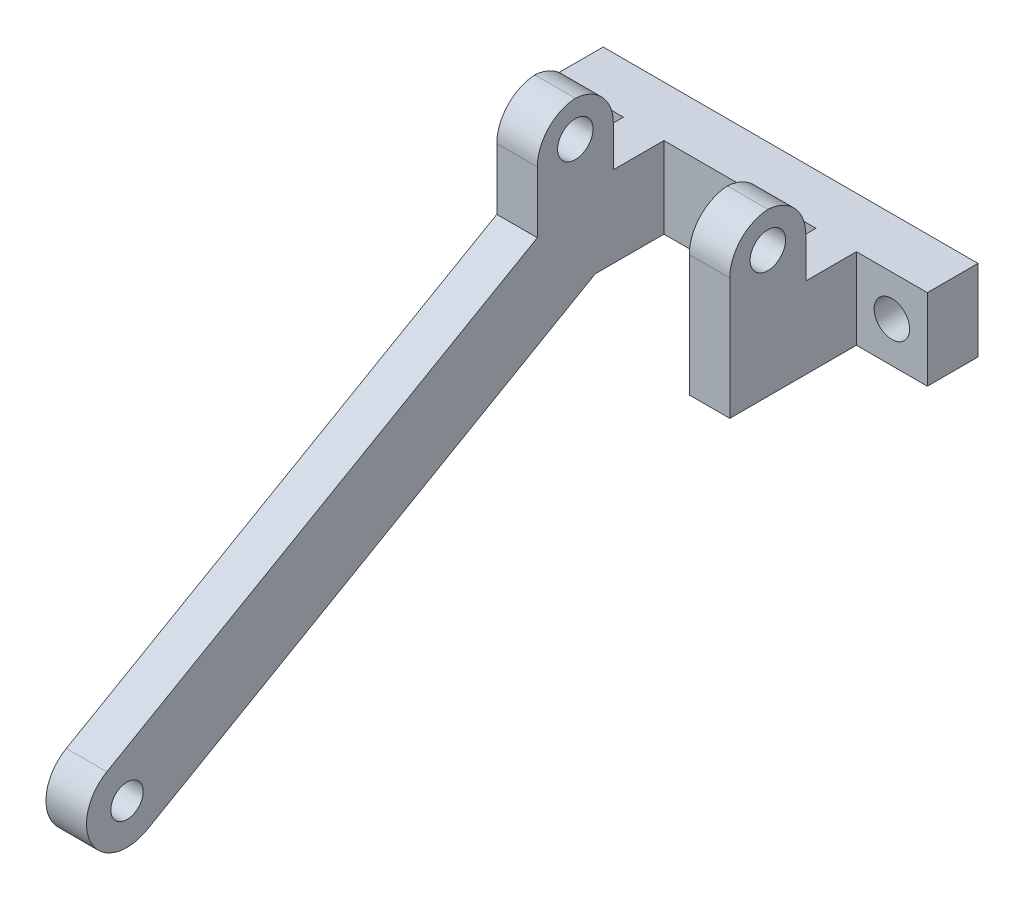
SolidWorks part; units mm, degrees
ref_plane "Front Plane" through (0, 0, 0) normal (0, 0, 1) x (1, 0, 0)
ref_plane "Top Plane" through (0, 0, 0) normal (0, 1, 0) x (1, 0, 0)
ref_plane "Right Plane" through (0, 0, 0) normal (1, 0, 0) x (0, 0, -1)
sketch "Sketch1" plane through (0, 0, 0) normal (0, 0, 1) x (1, 0, 0)
  line L0 (15, 0) -> (-15, 0) construction
  line L1 (-18.5, 4) -> (18.5, 4)
  line L2 (-18.5, 4) -> (-18.5, -4)
  line L3 (-18.5, -4) -> (18.5, -4)
  line L4 (18.5, 4) -> (18.5, -4)
  line L5 (-18.5, 4) -> (18.5, -4) construction
  line L6 (-18.5, -4) -> (18.5, 4) construction
  line L7 (0, -4) -> (0, 4) construction
  circle A0 centre (-15, 0) radius 1.75
  circle A1 centre (15, 0) radius 1.75
  point P0 (0, 0)
  point P12 (0, 0)
  dimension "D3" = 3.5
  dimension "D1" = 37
  dimension "D2" = 8
  dimension "D4" = 15
extrude "Boss-Extrude1" add sketch "Sketch1" along normal blind 5
sketch "Sketch2" plane through (0, 0, 5) normal (0, 0, 1) x (1, 0, 0)
  line L0 (0, 4) -> (0, -4) construction
  line L1 (18.5, 4) -> (-18.5, 4) construction
  line L2 (-18.5, -4) -> (18.5, -4) construction
  line L3 (11.5, -4) -> (7.5, 4) construction
  line L4 (-11.5, 4) -> (-7.5, 4)
  line L5 (-11.5, 4) -> (-11.5, -4)
  line L6 (-11.5, -4) -> (-7.5, -4)
  line L7 (-7.5, 4) -> (-7.5, -4)
  line L8 (-11.5, 4) -> (-7.5, -4) construction
  line L9 (-11.5, -4) -> (-7.5, 4) construction
  line L10 (11.5, 4) -> (7.5, -4) construction
  line L11 (7.5, 4) -> (7.5, -4)
  line L12 (11.5, -4) -> (7.5, -4)
  line L13 (11.5, 4) -> (11.5, -4)
  line L14 (11.5, 4) -> (7.5, 4)
  point P6 (-9.5, 0)
  point P15 (9.5, 0)
  dimension "D1" = 7.5
  dimension "D2" = 4
extrude "Boss-Extrude2" add sketch "Sketch2" along normal blind 12.5
sketch "Sketch4" plane through (0, 4, 0) normal (0, 1, 0) x (1, 0, 0)
  line L0 (-7.5, -17.5) -> (-7.5, -5) construction
  line L1 (-11.5, -17.5) -> (-7.5, -17.5)
  line L2 (-11.5, -17.5) -> (-11.5, -10)
  line L3 (-11.5, -10) -> (-7.5, -10)
  line L4 (-7.5, -17.5) -> (-7.5, -10)
  line L5 (0, 0) -> (0, -5) construction
  line L6 (7.5, -5) -> (-7.5, -5) construction
  line L7 (7.5, -17.5) -> (7.5, -10)
  line L8 (11.5, -10) -> (7.5, -10)
  line L9 (11.5, -17.5) -> (11.5, -10)
  line L10 (11.5, -17.5) -> (7.5, -17.5)
  dimension "D1" = 7.5
extrude "Boss-Extrude3" add sketch "Sketch4" along normal blind 8
sketch "Sketch3" plane through (-11.5, 0, 0) normal (-1, 0, 0) x (0, 0, 1)
  line L0 (10, 8.5) -> (17.5, 8.5) construction
  line L4 (10, 12) -> (10, 4) construction
  line L5 (17.5, 12) -> (17.5, -4) construction
  line L6 (13.75, 8.5) -> (13.75, 12) construction
  line L7 (10, 12) -> (17.5, 12) construction
  circle A0 centre (13.75, 8.5) radius 1.75
  dimension "D1" = 3.5
  dimension "D2" = 8.5
extrude "Cut-Extrude1" cut sketch "Sketch3" against normal through all
fillet "Fillet1" radius 4 4 edges at (-9.5, 12, 10) (9.5, 12, 10) (9.5, 12, 17.5) (-9.5, 12, 17.5)
sketch "Sketch5" plane through (-7.5, 0, 0) normal (1, 0, 0) x (0, 0, -1)
  line L0 (-10, 8) -> (-10, 4) construction
  line L1 (-10, 6.5) -> (-13, 6.5)
  line L2 (-10, 6.5) -> (-10, 1.5)
  line L3 (-10, 1.5) -> (-13, 1.5)
  line L4 (-13, 6.5) -> (-13, 1.5)
  line L5 (-10, 4) -> (-5, 4) construction
  dimension "D1" = 3
  dimension "D2" = 5
  dimension "D3" = 2.5
extrude "Boss-Extrude4" [suppressed] add sketch "Sketch5" along normal up to next
sketch "Sketch6" plane through (-11.5, 0, 0) normal (-1, 0, 0) x (0, 0, 1)
  line L0 (56.0113, -29.4012) -> (11.7824, -4)
  line L1 (17.5, -4) -> (5, -4) construction
  line L2 (11.7824, -4) -> (17.5, 1.9418)
  line L3 (13.75, 8.5) -> (58.0033, -25.9326) construction
  line L4 (17.5, 1.9418) -> (59.9954, -22.4639)
  line L5 (59.9954, -22.4639) -> (56.0113, -29.4012) construction
  line L6 (13.75, 8.5) -> (13.75, -4) construction
  line L7 (17.5, 8) -> (17.5, -4) construction
  circle A0 centre (58.0033, -25.9326) radius 1.6
  arc A1 (56.0113, -29.4012) -> (59.9954, -22.4639) centre (58.0033, -25.9326) ccw
  dimension "D1" = 3.2
  dimension "D2" = 8
  dimension "D3" = 52.114
  dimension "D4" = 56.071
  dimension "D5" = 1.9676
extrude "Boss-Extrude5" add sketch "Sketch6" against normal up to surface (4 mm away) up to face at (-7.5, 6.75, 13.75)
equation "\"X-ROD-SPACING\"=45"
equation "\"Y-ROD-SPACING\"=75"
equation "\"Z-ROD-SPACING\"=17.5"
equation "\"Y-BED-OFFSET\"=2"
equation "\"Y-BED-ROD-INSET\"=3.5"
equation "\"Y-BED-SCREW-SPACING\"=209"
equation "\"Y-BED-SCREW-CUTOUT-SLOT-HEIGHT\"=2"
equation "\"T-SLOT-NUT-FILLET-RADIUS\"=0.5"
equation "\"T-SLOT-SCREW-SHAFT-RADIUS\"=1.55"
equation "\"T-SLOT-SCREW-SHAFT-CUTOUT-LENGTH\"=11"
equation "\"T-SLOT-NUT-DEPTH\"=3.5"
equation "\"T-SLOT-NUT-WIDTH\"=2.85"
equation "\"T-SLOT-NUT-END-DISTANCE\"=8"
equation "\"ACRYLIC-THICKNESS\"=10"
equation "\"ACRYLIC-THICKNESS2\"=4.5"
equation "\"ACRYLIC-TAB-CUTOUT-SIZE\"=\"ACRYLIC-THICKNESS\"+\"ACRYLIC-TAB-TOLERANCE\"*2"
equation "\"ACRYLIC-TAB-TOLERANCE\"=-.05"
equation "\"ACRYLIC-TAB-WIDTH\"=\"ACRYLIC-THICKNESS\""
equation "\"ACRYLIC-M3-HOLE\"=2.9"
equation "\"SMOOTHROD-CAP-SCREW-DISTANCE\"=20"
equation "\"FRAME-WIDTH-INNER\"=370"
equation "\"NEMA17-HOLE-SPACING\"=31"
equation "\"NEMA17-CENTRAL-CUTOUT\"=22.5"
equation "\"Z-BRACKET-REACH\"=55"
equation "\"Z-ROD-INSET\"=13.5"
equation "\"TOP-BRACKET-SPACING\"=40"
equation "\"SMOOTHROD-X-LENGTH\"=350"
equation "\"SMOOTHROD-Y-LENGTH\"=350"
equation "\"SMOOTHROD-Z-LENGTH\"=350"
equation "\"SMOOTHROD-TIGHTENING-HEADROOM\"=.25"
equation "\"LEADSCREW-Z-LENGTH\"=300"
equation "\"SCREW-LENGTH-FRAME\"=\"ACRYLIC-THICKNESS\" + 10"
equation "\"SCREW-LENGTH-MOTOR\"=\"ACRYLIC-THICKNESS\" + 5"
equation "\"SCREW-LENGTH-EXTRUDER\"=28"
equation "\"SCREW-HEAD-RADIUS\"=6"
equation "\"PRINTED-X-SMOOTHROD-DIAMETER\"=9.0"
equation "\"PRINTED-X-SMOOTHROD-CUTOUT\"=10"
equation "\"PRINTED-X-BASE-HEIGHT\"=10"
equation "\"PRINTED-LM8UU-CUTOUT-SIZE\"=15.5"
equation "\"PRINTED-LM8UU-CUTOUT-LENGTH\"=24.5"
equation "\"PRINTED-X-IDLER-HEIGHT\"=16"
equation "\"PSU-MOUNTING-WIDTH\"=95"
equation "\"PSU-MOUNTING-HEIGHT\"=177"
equation "\"Y-BELT-TO-ROD-DISTANCE\"=20"
equation "\"SPOOL-HOLDER-ROD-SPACING\"=150"
equation "\"ACRYLIC-X-CARRIAGE-WIDTH\"=55"
equation "\"ACRYLIC-X-CARRIAGE-HEIGHT\"=75"
equation "\"ACRYLIC-X-CARRIAGE-LM8UU-CUTOUT-WIDTH\"=24.25"
equation "\"ACRYLIC-X-CARRIAGE-LM8UU-CUTOUT-HEIGHT\"=11.0"
equation "\"ACRYLIC-X-CARRIAGE-SCREW-SPACING-X\"=15"
equation "\"ACRYLIC-X-CARRIAGE-SCREW-SPACING-Y\"=33"
equation "\"ACRYLIC-X-CARRIAGE-CENTER-TAB-SPACING\"=14"
equation "\"ACRYLIC-X-CARRIAGE-EXTRUDER-OFFSET\"=26"
equation "\"ACRYLIC-X-CARRIAGE-EXTRUDER-ANGLE\"=90"
equation "\"ACRYLIC-X-CARRIAGE-EXTRUDER-SHELF-DEPTH\"=\"ACRYLIC-X-CARRIAGE-EXTRUDER-OFFSET\" + 28"
equation "\"ACRYLIC-X-CARRIAGE-EXTRUDER-BRACE-SPACING\"=23"
equation "\"ACRYLIC-X-CARRIAGE-EXTRUDER-BRACE-TAB-OFFSET\"=20"
equation "\"ACRYLIC-X-CARRIAGE-EXTRUDER-BRACE-HEIGHT\"=35"
equation "\"ACRYLIC-X-CARRIAGE-EXTRUDER-BRACE-SCREW-SPACING\"=22"
equation "\"ACRYLIC-X-CARRIAGE-DUAL-WIDTH-MULTIPLIER\"=1.65"
equation "\"ACRYLIC-X-CARRIAGE-DUAL-HOTEND-SPACING\"=42"
equation "\"ACRYLIC-X-CARRIAGE-DUAL-WIDTH\"=75"
equation "\"ACRYLIC-X-CARRIAGE-DUAL-HOTEND-SEPARATION\"=36"
equation "\"ACRYLIC-X-CARRIAGE-DUAL-MOUNT-PLATE-DEPTH\"=75"
equation "\"ACRYLIC-X-CARRIAGE-DUAL-MOUNT-BRACE-WIDTH\"=33"
equation "\"ACRYLIC-X-CARRIAGE-DUAL-MOUNT-SCREW-WIDTH\"=40"
equation "\"D3@Sketch1\"=3.5"
equation "\"PRINTED-M3-HOLE\"=3.5"
equation "\"BLOWER-FAN-WIDTH\"=15"
equation "\"D1@Sketch2\"=\"BLOWER-FAN-WIDTH\"/2"
